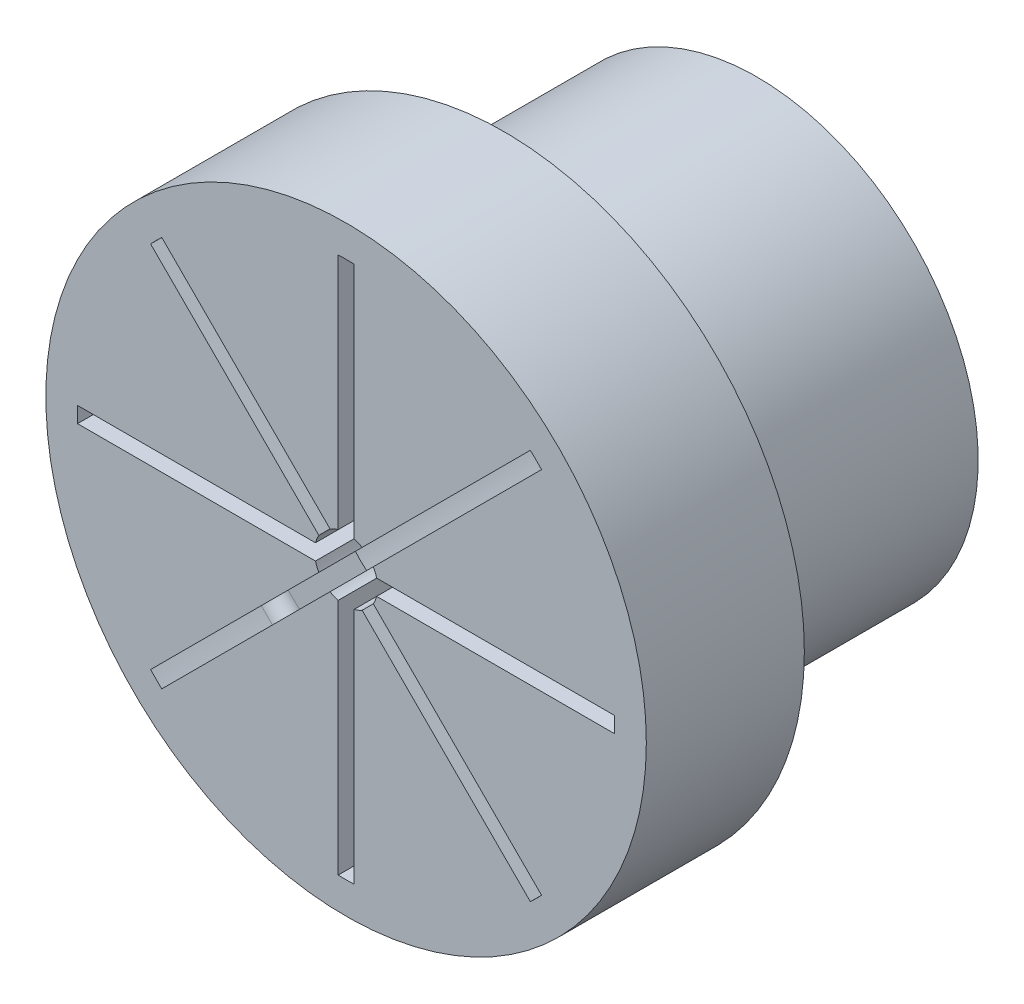
SolidWorks part; units mm, degrees
ref_plane "Front Plane" through (0, 0, 0) normal (0, 0, 1) x (1, 0, 0)
ref_plane "Top Plane" through (0, 0, 0) normal (0, 1, 0) x (1, 0, 0)
ref_plane "Right Plane" through (0, 0, 0) normal (1, 0, 0) x (0, 0, -1)
sketch "Sketch1" plane through (0, 0, 0) normal (0, 0, 1) x (1, 0, 0)
  circle A0 centre (0, 0) radius 7
  circle A1 centre (0, 0) radius 7.5 construction
  circle A2 centre (0, 0) radius 7.5 construction
  dimension "D1" = 0.5
extrude "Boss-Extrude1" add sketch "Sketch1" along normal blind 10
sketch "Sketch2" plane through (0, 0, 10) normal (0, 0, 1) x (1, 0, 0)
  circle A0 centre (0, 0) radius 9.5
  circle A1 centre (0, 0) radius 10 construction
  circle A2 centre (0, 0) radius 10 construction
  dimension "D1" = 0.5
extrude "Boss-Extrude2" add sketch "Sketch2" along normal up to surface (5 mm away)
sketch "Sketch3" plane through (0, 0, 0) normal (0, 0, -1) x (-1, 0, 0)
  circle A0 centre (0, 0) radius 5
  circle A1 centre (0, 0) radius 7 construction
  dimension "D1" = 2
extrude "Cut-Extrude1" cut sketch "Sketch3" against normal offset from surface (13 mm away) 2 up to face at (9.5, 0, 15)
ref_plane "Plane1" through (0, 0, 11) normal (0, 0, -1) x (-1, 0, 0)
sketch "Sketch4" plane through (0, 0, 11) normal (0, 0, -1) x (-1, 0, 0)
  circle A0 centre (0, 0) radius 8.5
  circle A1 centre (0, 0) radius 9.5 construction
  dimension "D1" = 1
extrude "Cut-Extrude2" cut sketch "Sketch4" against normal up to surface (2 mm away) up to face at (5, 0, 13)
sketch "Sketch5" plane through (0, 0, 15) normal (0, 0, 1) x (1, 0, 0)
  line L0 (0, 0) -> (0, 1) construction
  line L1 (0, 0) -> (-0.7071, 0.7071) construction
  line L2 (0, 0) -> (-1, 0) construction
  line L3 (0, 0) -> (0, -1) construction
  line L4 (0, 0) -> (-0.7071, -0.7071) construction
  line L5 (0, 0) -> (1, 0) construction
  line L6 (0, 0) -> (0.7071, 0.7071) construction
  line L7 (0, 0) -> (0.7071, -0.7071) construction
  line L8 (-0.25, 1) -> (0.25, 1) construction
  line L9 (0.5303, 0.8839) -> (0.8839, 0.5303) construction
  line L10 (1, 0.25) -> (1, -0.25) construction
  line L11 (0.8839, -0.5303) -> (0.5303, -0.8839) construction
  line L12 (0.25, -1) -> (-0.25, -1) construction
  line L13 (-0.5303, -0.8839) -> (-0.8839, -0.5303) construction
  line L14 (-1, 0.25) -> (-1, -0.25) construction
  line L15 (-0.5303, 0.8839) -> (-0.8839, 0.5303) construction
  line L16 (-0.25, 1) -> (-0.25, 8.4963)
  line L17 (0.25, 1) -> (0.25, 8.4963)
  line L18 (-0.25, 1) -> (-0.25, 0.9682)
  line L19 (0.25, 1) -> (0.25, 0.9682)
  line L20 (0.5303, 0.8839) -> (5.831, 6.1846)
  line L21 (0.5303, 0.8839) -> (0.5079, 0.8614)
  line L22 (0.8839, 0.5303) -> (0.8614, 0.5079)
  line L23 (0.8839, 0.5303) -> (6.1846, 5.831)
  line L24 (1, 0.25) -> (8.4963, 0.25)
  line L25 (1, -0.25) -> (8.4963, -0.25)
  line L26 (1, 0.25) -> (0.9682, 0.25)
  line L27 (1, -0.25) -> (0.9682, -0.25)
  line L28 (0.5303, -0.8839) -> (5.831, -6.1846)
  line L29 (0.8839, -0.5303) -> (6.1846, -5.831)
  line L30 (0.8839, -0.5303) -> (0.8614, -0.5079)
  line L31 (0.5079, -0.8614) -> (0.5303, -0.8839)
  line L32 (0.25, -1) -> (0.25, -8.4963)
  line L33 (0.25, -1) -> (0.25, -0.9682)
  line L34 (-0.25, -1) -> (-0.25, -8.4963)
  line L35 (-0.25, -1) -> (-0.25, -0.9682)
  line L36 (-0.5303, -0.8839) -> (-5.831, -6.1846)
  line L37 (-0.8839, -0.5303) -> (-6.1846, -5.831)
  line L38 (-0.5303, -0.8839) -> (-0.5079, -0.8614)
  line L39 (-0.8839, -0.5303) -> (-0.8614, -0.5079)
  line L40 (-1, 0.25) -> (-8.4963, 0.25)
  line L41 (-1, -0.25) -> (-8.4963, -0.25)
  line L42 (-1, 0.25) -> (-0.9682, 0.25)
  line L43 (-1, -0.25) -> (-0.9682, -0.25)
  line L44 (-0.8839, 0.5303) -> (-6.1846, 5.831)
  line L45 (-0.5303, 0.8839) -> (-5.831, 6.1846)
  line L46 (-0.8839, 0.5303) -> (-0.8614, 0.5079)
  line L47 (-0.5303, 0.8839) -> (-0.5079, 0.8614)
  circle A0 centre (0, 0) radius 1 construction
  circle A1 centre (0, 0) radius 8.5 construction
  circle A2 centre (0, 0) radius 8.5 construction
  arc A3 (-6.1846, 5.831) -> (-5.831, 6.1846) centre (0, 0) cw
  arc A4 (-0.25, 8.4963) -> (0.25, 8.4963) centre (0, 0) cw
  arc A5 (5.831, 6.1846) -> (6.1846, 5.831) centre (0, 0) cw
  arc A6 (8.4963, 0.25) -> (8.4963, -0.25) centre (0, 0) cw
  arc A7 (-0.25, -8.4963) -> (0.25, -8.4963) centre (0, 0) ccw
  arc A8 (-6.1846, -5.831) -> (-5.831, -6.1846) centre (0, 0) ccw
  arc A9 (-8.4963, 0.25) -> (-8.4963, -0.25) centre (0, 0) ccw
  arc A10 (5.831, -6.1846) -> (6.1846, -5.831) centre (0, 0) ccw
  arc A11 (-0.9682, 0.25) -> (-0.8614, 0.5079) centre (0, 0) cw
  arc A12 (-0.5079, 0.8614) -> (-0.25, 0.9682) centre (0, 0) cw
  arc A13 (0.25, 0.9682) -> (0.5079, 0.8614) centre (0, 0) cw
  arc A14 (0.8614, 0.5079) -> (0.9682, 0.25) centre (0, 0) cw
  arc A15 (0.8614, -0.5079) -> (0.9682, -0.25) centre (0, 0) ccw
  arc A16 (0.25, -0.9682) -> (0.5079, -0.8614) centre (0, 0) ccw
  arc A17 (-0.5079, -0.8614) -> (-0.25, -0.9682) centre (0, 0) ccw
  arc A18 (-0.9682, -0.25) -> (-0.8614, -0.5079) centre (0, 0) ccw
  point P14 (0, 1)
  point P17 (0.7071, 0.7071)
  point P20 (1, 0)
  point P23 (0.7071, -0.7071)
  point P26 (0, -1)
  point P29 (-0.7071, -0.7071)
  point P32 (-1, 0)
  point P35 (-0.7071, 0.7071)
  dimension "D1" = 2
  dimension "D2" = 45
  dimension "D3" = 0.5
extrude "Cut-Extrude3" cut sketch "Sketch5" against normal up to next
fillet "Fillet1" radius 0.5 9 edges at (-3.2528, 7.853, 13) (-7.853, 3.2528, 13) (-7.853, -3.2528, 13) (-3.2528, -7.853, 13) (3.2528, -7.853, 13) (-8.5, 0, 11) (7.853, -3.2528, 13) (7.853, 3.2528, 13) (3.2528, 7.853, 13)
sketch "Sketch6" plane through (0, 0, 0) normal (0, 0, -1) x (-1, 0, 0)
  circle A0 centre (0, 0) radius 7
  circle A1 centre (0, 0) radius 7 construction
extrude "Cut-Extrude4" cut sketch "Sketch6" against normal blind 2
